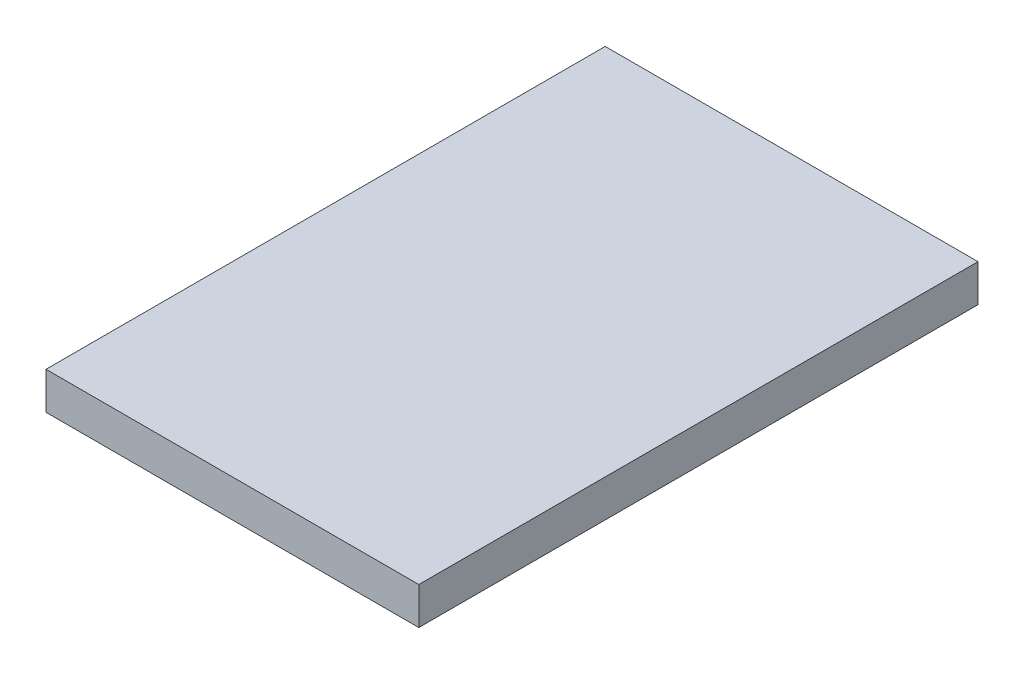
SolidWorks part; units mm, degrees
ref_plane "Front Plane" through (0, 0, 0) normal (0, 0, 1) x (1, 0, 0)
ref_plane "Top Plane" through (0, 0, 0) normal (0, 1, 0) x (1, 0, 0)
ref_plane "Right Plane" through (0, 0, 0) normal (1, 0, 0) x (0, 0, -1)
sketch "Sketch1" plane through (0, 0, 0) normal (0, 1, 0) x (1, 0, 0)
  line L1 (-24.5, -50.5) -> (24.5, -50.5)
  line L2 (-24.5, -50.5) -> (-24.5, 50.5)
  line L3 (-24.5, 50.5) -> (24.5, 50.5)
  line L4 (24.5, -50.5) -> (24.5, 50.5)
  line L5 (-24.5, -50.5) -> (24.5, 50.5) construction
  line L6 (-24.5, 50.5) -> (24.5, -50.5) construction
  point P0 (0, 0)
  dimension "D1" = 49
  dimension "D2" = 101
extrude "Boss-Extrude1" add sketch "Sketch1" along normal blind 1.5
sketch "Sketch2" plane through (0, 0, 0) normal (0, 1, 0) x (1, 0, 0)
  line L4 (24.5, -50.5) -> (24.5, 50.5)
  line L5 (24.5, 50.5) -> (-24.5, 50.5)
  line L6 (-24.5, 50.5) -> (-24.5, -50.5)
  line L7 (-24.5, -50.5) -> (24.5, -50.5)
  line L8 (24.5, -50.5) -> (24.5, 50.5)
  line L9 (24.5, 50.5) -> (-24.5, 50.5)
  line L10 (-24.5, 50.5) -> (-24.5, -50.5)
  line L11 (-24.5, -50.5) -> (24.5, -50.5)
  line L16 (27, -53) -> (27, 53)
  line L17 (27, 53) -> (-27, 53)
  line L18 (-27, 53) -> (-27, -53)
  line L19 (-27, -53) -> (27, -53)
  line L20 (27, -53) -> (27, 53)
  line L21 (27, 53) -> (-27, 53)
  line L22 (-27, 53) -> (-27, -53)
  line L23 (-27, -53) -> (27, -53)
  dimension "D1" = 0
  dimension "D2" = 2.5
extrude "Boss-Extrude2" add sketch "Sketch2" along normal blind 4
sketch "Sketch3" plane through (0, 0, 0) normal (0, 1, 0) x (1, 0, 0)
  line L0 (24.5, -50.5) -> (-24.5, -50.5) construction
  line L2 (-24.5, 50.5) -> (-24.5, -50.5) construction
  line L3 (-24.5, -30.7417) -> (-24.5, -34.0583)
  line L8 (-24.5, -46.4033) -> (-24.5, -50.5)
  line L9 (-24.5, 50.5) -> (-24.5, -50.5) construction
  line L10 (-24.5, -50.5) -> (-20.4033, -50.5)
  line L11 (-24.5, -50.5) -> (24.5, -50.5) construction
  arc A1 (-24.5, -34.0583) -> (-24.5, -30.7417) centre (-22, -32.4) ccw
  arc A2 (-20.4033, -50.5) -> (-24.5, -46.4033) centre (-21.9, -47.9) ccw
  dimension "D5" = 6
  dimension "D1" = 2.6
  dimension "D3" = 2.5
  dimension "D4" = 18.1
extrude "Boss-Extrude3" add sketch "Sketch3" along normal up to surface (4 mm away) up to face at (0, 4, 0)
sketch "Sketch8" plane through (0, 1.5, 0) normal (0, 1, 0) x (1, 0, 0)
  line L0 (0, 0) -> (-24.5, 0) construction
  line L1 (-14.75, 7.5) -> (-9.75, 7.5)
  line L2 (-14.75, 7.5) -> (-14.75, -7.5)
  line L3 (-14.75, -7.5) -> (-9.75, -7.5)
  line L4 (-9.75, 7.5) -> (-9.75, -7.5)
  line L5 (-24.5, 50.5) -> (-24.5, -30.7417) construction
  point P4 (-9.75, 0)
  point P11 (-12.25, 0)
  point P12 (-12.25, 7.5)
  dimension "D1" = 15
  dimension "D2" = 5
extrude "Boss-Extrude4" add sketch "Sketch8" along normal offset from surface (3.5 mm away) 1 up to face at (0, 4, 0) offset beyond the face yes
fillet "Fillet3" radius 4 4 edges at (-12.25, 1.5, -7.5) (-9.75, 1.5, 0) (-14.75, 1.5, 0) (-12.25, 1.5, 7.5)
mirror "Mirror1" about plane through (0, 0, 0) normal (1, 0, 0) of "Fillet3", "Boss-Extrude3", "Boss-Extrude4"
sketch "Sketch4" plane through (0, 4, 0) normal (0, 1, 0) x (1, 0, 0)
  circle A0 centre (-21.9, -47.9) radius 1.75
  circle A1 centre (21.9, -47.9) radius 1.75
  arc A2 (-20.4033, -50.5) -> (-24.5, -46.4033) centre (-21.9, -47.9) ccw construction
  arc A3 (24.5, -46.4033) -> (20.4033, -50.5) centre (21.9, -47.9) ccw construction
  dimension "D1" = 3.5
  dimension "D2" = 3.5
extrude "Cut-Extrude1" cut sketch "Sketch4" against normal blind 1
sketch "Sketch5" plane through (0, 4, 0) normal (0, 1, 0) x (1, 0, 0)
  circle A0 centre (-22, -32.4) radius 1.75
  circle A1 centre (22, -32.4) radius 1.75
  dimension "D1" = 3.5
  dimension "D2" = 3.5
extrude "Cut-Extrude2" cut sketch "Sketch5" against normal blind 1
sketch "Sketch6" plane through (0, 0, 0) normal (0, 1, 0) x (1, 0, 0)
  line L1 (-9, -45) -> (5.5, -45)
  line L2 (-9, -45) -> (-9, -52.3)
  line L3 (-9, -52.3) -> (5.5, -52.3)
  line L4 (5.5, -45) -> (5.5, -52.3)
  line L8 (-20.4033, -50.5) -> (20.4033, -50.5) construction
  line L10 (24.5, -46.4033) -> (24.5, -34.0583) construction
  line L11 (-24.5, -34.0583) -> (-24.5, -46.4033) construction
  line L13 (-27, -53) -> (27, -53) construction
  dimension "D1" = 15.5
  dimension "D2" = 19
  dimension "D3" = 0.7
  dimension "D4" = 5.5
extrude "Cut-Extrude3" [suppressed] cut sketch "Sketch6" along normal through all
sketch "Sketch7" plane through (0, 0, 0) normal (0, 1, 0) x (1, 0, 0)
  line L0 (-27, -53) -> (27, -53) construction
  line L1 (18.3, -47.7) -> (6.5, -47.7)
  line L2 (18.3, -47.7) -> (18.3, -43.7)
  line L3 (18.3, -43.7) -> (6.5, -43.7)
  line L4 (6.5, -47.7) -> (6.5, -43.7)
  line L6 (-27, -53) -> (27, -53) construction
  line L7 (27, -53) -> (27, 53) construction
  point P10 (12.4, -43.7)
  dimension "D1" = 11.8
  dimension "D3" = 9.3
  dimension "D4" = 5.3
  dimension "D5" = 14.6
extrude "Cut-Extrude4" [suppressed] cut sketch "Sketch7" along normal through all
fillet "Fillet1" radius 3 4 edges at (-27, 2, 53) (27, 2, 53) (27, 2, -53) (-27, 2, -53)
fillet "Fillet2" radius 10 4 edges at (24.5, 2.75, 30.7417) (24.5, 2.75, 34.0583) (-24.5, 2.75, 30.7417) (-24.5, 2.75, 34.0583)
chamfer "Chamfer1" distance 1 angle 45 2 edges at (-22, 3, 34.15) (22, 3, 34.15)
chamfer "Chamfer2" distance 1 angle 45 2 edges at (-21.9, 3, 49.65) (21.9, 3, 49.65)
fillet "Fillet4" radius 2 4 edges at (24.5, 2.75, 46.4033) (20.4033, 2.75, 50.5) (-20.4033, 2.75, 50.5) (-24.5, 2.75, 46.4033)
fillet "Fillet6" radius 4 2 edges at (24.5, 2.75, -50.5) (-24.5, 2.75, -50.5)
fillet "Fillet5" radius 1 3 edges at (24.5, 1.5, -12.3592) (0, 1.5, -50.5) (-24.5, 1.5, -12.3592) type face fillet first side face at (12.25, 1.5, 0) second side face at (24.5, 2.75, -12.3592) second side face at (0, 2.75, -50.5) second side face at (-24.5, 2.75, -12.3592)
fillet "Fillet7" [suppressed] radius 2
sketch "Sketch9" plane through (0, 0, 0) normal (0, 1, 0) x (1, 0, 0)
  line L1 (-50, 75) -> (50, 75)
  line L2 (-50, 75) -> (-50, -75)
  line L3 (-50, -75) -> (50, -75)
  line L4 (50, 75) -> (50, -75)
  line L5 (-50, 75) -> (50, -75) construction
  line L6 (-50, -75) -> (50, 75) construction
  point P0 (0, 0)
  dimension "D1" = 150
  dimension "D2" = 100
extrude "Boss-Extrude5" add sketch "Sketch9" along normal blind 10 separate body
combine bodies "Combine1" operation type subtract main body 110 bodies to subtract 106
sketch "Sketch10" [suppressed] plane through (0, 4, 0) normal (0, 1, 0) x (1, 0, 0)
  line L1 (-50, 75) -> (50, 75)
  line L2 (-50, 75) -> (-50, -75)
  line L3 (-50, -75) -> (50, -75)
  line L4 (50, 75) -> (50, -75)
  line L5 (-50, 75) -> (50, -75) construction
  line L6 (-50, -75) -> (50, 75) construction
  point P0 (0, 0)
  dimension "D1" = 100
  dimension "D2" = 150
extrude "Boss-Extrude6" [suppressed] add sketch "Sketch10" against normal blind 10
combine bodies "Combine2" [suppressed] operation type subtract main body 115 bodies to subtract 106
sketch "Sketch13" [suppressed] plane through (0, 4, 0) normal (0, 1, 0) x (1, 0, 0)
  line L0 (20.5, 50.5) -> (-20.5, 50.5) construction
  line L1 (-24.5, 46.5) -> (-24.5, -50.5) construction
  line L2 (-24.5, -50.5) -> (24.5, -50.5) construction
  line L3 (24.5, 46.5) -> (24.5, -50.5) construction
  line L4 (20.5, 50.5) -> (-20.5, 50.5)
  line L5 (-24.5, 46.5) -> (-24.5, -50.5)
  line L6 (-24.5, -50.5) -> (24.5, -50.5)
  line L7 (24.5, 46.5) -> (24.5, -50.5)
  arc A1 (-20.5, 50.5) -> (-24.5, 46.5) centre (-20.5, 46.5) ccw construction
  arc A2 (24.5, 46.5) -> (20.5, 50.5) centre (20.5, 46.5) ccw construction
  arc A3 (-20.5, 50.5) -> (-24.5, 46.5) centre (-20.5, 46.5) ccw
  arc A4 (24.5, 46.5) -> (20.5, 50.5) centre (20.5, 46.5) ccw
extrude "Boss-Extrude8" [suppressed] add sketch "Sketch13" against normal up to surface (4 mm away)
scale "Scale1" scale about centroid uniform scaling yes scale factor 0.99
sketch "Sketch12" [suppressed] plane through (0, 3.9802, 0) normal (0, 1, 0) x (1, 0, 0)
  line L1 (-50, -75) -> (50, -75)
  line L2 (-50, -75) -> (-50, 75)
  line L3 (-50, 75) -> (50, 75)
  line L4 (50, -75) -> (50, 75)
  line L5 (-50, -75) -> (50, 75) construction
  line L6 (-50, 75) -> (50, -75) construction
  point P0 (0, 0)
  dimension "D1" = 150
  dimension "D2" = 100
extrude "Boss-Extrude7" [suppressed] add sketch "Sketch12" along normal blind 3
shell "Shell4" [suppressed] thickness 1
chamfer "Chamfer3" distance 3 angle 45 8 edges at (26.73, 0.0532, -0.001) (25.8601, 0.0532, -51.6011) (25.8601, 0.0532, 51.5992) (0, 0.0532, -52.471) (0, 0.0532, 52.469) (-25.8601, 0.0532, -51.6011) (-25.8601, 0.0532, 51.5992) (-26.73, 0.0532, -0.001)
